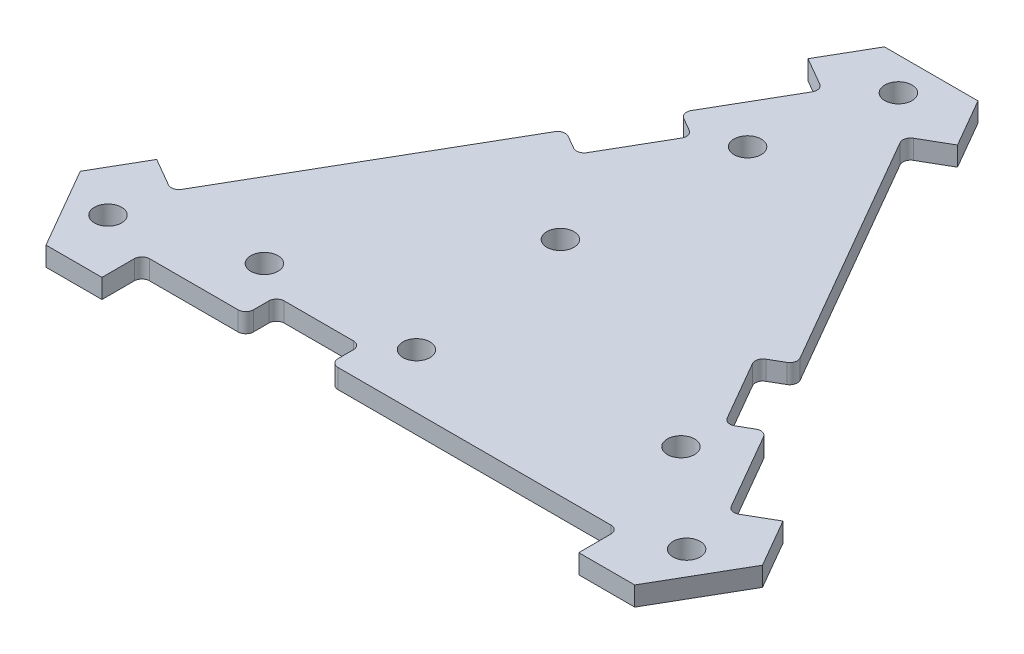
SolidWorks part; units mm, degrees
ref_plane "Front Plane" through (0, 0, 0) normal (0, 0, 1) x (1, 0, 0)
ref_plane "Top Plane" through (0, 0, 0) normal (0, 1, 0) x (1, 0, 0)
ref_plane "Right Plane" through (0, 0, 0) normal (1, 0, 0) x (0, 0, -1)
sketch "Sketch1" plane through (0, 0, 0) normal (0, 1, 0) x (1, 0, 0)
  line L1 (48.6116, -36.9866) -> (56.3371, -23.6056) construction
  line L3 (-56.3371, -23.6056) -> (-48.6116, -36.9866) construction
  line L4 (48.6116, -36.9866) -> (56.3371, -23.6056)
  line L5 (7.7256, 60.5922) -> (-7.7256, 60.5922) construction
  line L6 (-48.6116, -36.9866) -> (48.6116, -36.9866)
  line L7 (56.3371, -23.6056) -> (7.7256, 60.5922)
  line L8 (-7.7256, 60.5922) -> (-56.3371, -23.6056)
  line L9 (7.7256, 60.5922) -> (-7.7256, 60.5922)
  line L10 (-56.3371, -23.6056) -> (-48.6116, -36.9866)
extrude "Boss-Extrude1" add sketch "Sketch1" against normal blind 3.175
sketch "Sketch2" plane through (0, 0, 0) normal (0, 1, 0) x (1, 0, 0)
  line L0 (-48.6116, -36.9866) -> (48.6116, -36.9866) construction
  line L1 (-39.37, -36.9866) -> (39.37, -36.9866)
  line L2 (-39.37, -36.9866) -> (-39.37, -30.3826)
  line L3 (-39.37, -30.3826) -> (39.37, -30.3826)
  line L4 (39.37, -36.9866) -> (39.37, -44.2891) construction
  line L5 (-39.37, -44.2891) -> (-39.37, -36.9866) construction
  line L6 (39.37, -36.9866) -> (39.37, -30.3826)
  dimension "D1" = 6.604
extrude "Cut-Extrude1" cut sketch "Sketch2" against normal through all
ref_axis "Axis1" through (0, 0.1588, 0) along (0, -1, 0)
sketch "Sketch8" plane through (0, 0, 0) normal (0, 1, 0) x (1, 0, 0)
  line L0 (-39.37, -30.3826) -> (39.37, -30.3826) construction
  line L1 (-22.225, -30.3826) -> (-8.255, -30.3826)
  line L2 (-22.225, -30.3826) -> (-22.225, -25.3026)
  line L3 (-22.225, -25.3026) -> (-8.255, -25.3026)
  line L4 (-8.255, -30.3826) -> (-8.255, -25.3026)
  line L5 (-15.24, -25.3026) -> (-15.24, -30.3826) construction
  dimension "D1" = 13.97
  dimension "D2" = 5.08
  dimension "D3" = 15.24
extrude "Cut-Extrude2" cut sketch "Sketch8" against normal through all
fillet "Fillet1" radius 1.27 6 edges at (-39.37, -1.5875, 30.3826) (39.37, -1.5875, 30.3826) (-8.255, -1.5875, 25.3026) (-22.225, -1.5875, 25.3026) (-8.255, -1.5875, 30.3826) (-22.225, -1.5875, 30.3826)
hole_wizard "#8 Clearance Hole1" positions "Sketch6" profile "Sketch7" hole size "#8" standard "ANSI Inch" end condition through all
sketch "Sketch6" plane through (0, 0, 0) normal (0, 1, 0) x (1, 0, 0)
  circle A0 centre (-47.7802, -27.5859) radius 2.2479 construction
  point P0 (-47.7802, -27.5859)
sketch "Sketch7" plane through (-47.7802, 0, 27.5859) normal (1, 0, 0) x (0, 0, 1)
  line L0 (0, 0) -> (0, 3.175)
  line L1 (0, 3.175) -> (2.2479, 3.175)
  line L2 (2.2479, 3.175) -> (2.2479, 0)
  line L5 (2.2479, 0) -> (0, 0)
  line L11 (0, -6.35) -> (0, 107.95) construction
  dimension "Thru Hole Dia." = 4.4958
  dimension "Thru Hole Depth" = 3.175
pattern_circular "CirPattern1" count 3 over 360 about axis through (0, 0.1588, 0) along (0, -1, 0) of "Cut-Extrude1", "#8 Clearance Hole1", "Fillet1", "Cut-Extrude2"
hole_wizard "#8 Clearance Hole2" positions "Sketch3" profile "Sketch4" hole size "#8" standard "ANSI Inch" end condition through all
sketch "Sketch3" plane through (0, 0, 0) normal (0, 1, 0) x (1, 0, 0)
  point P9 (-27.94, -21.59)
  dimension "D1" = 27.94
  dimension "D2" = 21.59
sketch "Sketch4" plane through (-27.94, 0, 21.59) normal (1, 0, 0) x (0, 0, 1)
  line L0 (0, 0) -> (0, 3.175)
  line L1 (0, 3.175) -> (2.2479, 3.175)
  line L2 (2.2479, 3.175) -> (2.2479, 0)
  line L5 (2.2479, 0) -> (0, 0)
  line L11 (0, -6.35) -> (0, 107.95) construction
  dimension "Thru Hole Dia." = 4.4958
  dimension "Thru Hole Depth" = 3.175
ref_axis "Axis2" through (0, 8.0347, 0) along (0, -1, 0)
pattern_circular "CirPattern2" count 3 over 360 about axis through (0, 8.0347, 0) along (0, -1, 0) of "#8 Clearance Hole2"
hole_wizard "#8 Clearance Hole3" positions "Sketch11" profile "Sketch12" hole size "#8" standard "ANSI Inch" end condition through all
sketch "Sketch11" plane through (0, 0, 0) normal (0, 1, 0) x (1, 0, 0)
  circle A0 centre (-3.048, -21.3656) radius 3.429 construction
  point P0 (-6.9344, 6.2865)
  point P3 (-3.048, -21.3656)
sketch "Sketch12" plane through (-6.9344, 0, -6.2865) normal (1, 0, 0) x (0, 0, 1)
  line L0 (0, 0) -> (0, 3.175)
  line L1 (0, 3.175) -> (2.2479, 3.175)
  line L2 (2.2479, 3.175) -> (2.2479, 0)
  line L5 (2.2479, 0) -> (0, 0)
  line L11 (0, -6.35) -> (0, 107.95) construction
  dimension "Thru Hole Dia." = 4.4958
  dimension "Thru Hole Depth" = 3.175
